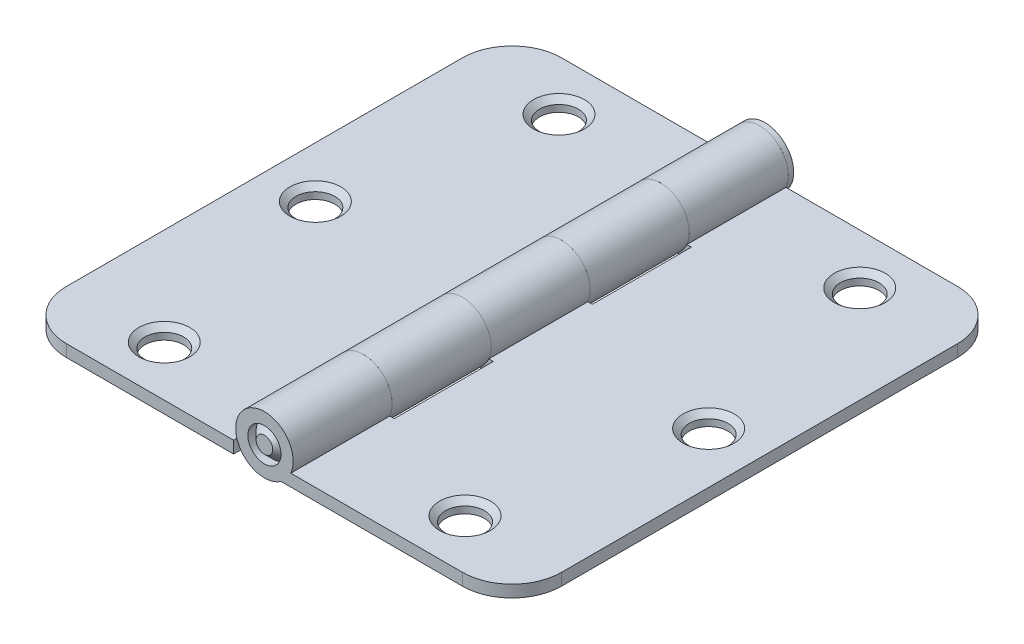
SolidWorks part; units mm, degrees
ref_plane "Front Plane" through (0, 0, 0) normal (0, 0, 1) x (1, 0, 0)
ref_plane "Top Plane" through (0, 0, 0) normal (0, 1, 0) x (1, 0, 0)
ref_plane "Right Plane" through (0, 0, 0) normal (1, 0, 0) x (0, 0, -1)
sketch "Sketch24" plane through (0, 0, 0) normal (0, 0, 1) x (1, 0, 0)
  line L0 (4.7324, -2.0552) -> (44.45, -2.0552) construction
  line L1 (44.45, -2.0552) -> (44.45, -4.2142) construction
  line L2 (44.45, -4.2142) -> (2.9766, -4.2142) construction
  line L3 (2.9766, -4.2142) -> (-2.9766, -4.2142) construction
  line L4 (-2.9766, -4.2142) -> (-44.45, -4.2142) construction
  line L5 (-44.45, -4.2142) -> (-44.45, -2.0552) construction
  line L6 (-44.45, -2.0552) -> (-4.7324, -2.0552) construction
  line L7 (-4.7324, -2.0552) -> (4.7324, -2.0552) construction
  line L8 (-5.5404, -2.0552) -> (-5.5404, -4.2142) construction
  line L9 (-5.1594, 0) -> (0, 0) construction
  line L10 (0, 0) -> (5.1594, 0) construction
  line L11 (2.9766, 0) -> (2.9766, -4.2142) construction
  circle A0 centre (0, 0) radius 2.9766 construction
  circle A1 centre (0, 0) radius 5.1594 construction
  dimension "Pin Diameter" = 5.9531
  dimension "Knuckle Diameter" = 10.3187
  dimension "Overall Width" = 88.9
  dimension "Leaf Thickness" = 2.159
  dimension "D1" = 0.381
  dimension "Door Leaf Width" = 44.45
  dimension "Frame Leaf Width" = 44.45
sketch "Sketch25" plane through (0, 0, 0) normal (0, 1, 0) x (1, 0, 0)
  line L0 (0, 0) -> (0, -44.45) construction
  line L1 (0, 0) -> (0, 44.45) construction
  line L2 (-27.0002, 0) -> (-27.0002, 35.433) construction
  line L3 (-2.9766, 0) -> (-44.45, 0) construction
  line L4 (-27.0002, 0) -> (-27.0002, -35.433) construction
  line L5 (-44.45, 0) -> (-44.45, -44.45) construction
  line L6 (-44.45, 0) -> (0, 0) construction
  line L7 (0, 0) -> (44.45, 0) construction
  line L8 (44.45, 0) -> (44.45, -44.45) construction
  circle A0 centre (-27.0002, 35.433) radius 3.4925 construction
  circle A1 centre (-27.0002, -35.433) radius 3.4925 construction
  circle A2 centre (-35.306, 0) radius 3.4925 construction
  point P10 (-30.4927, -35.433)
  point P12 (-30.4927, 35.433)
  point P13 (-27.0002, 0)
  point P14 (-27.0002, 38.9255)
  dimension "Hole Diameter" = 6.985
  dimension "Door Leaf Height" = 88.9
  dimension "Side to Side" = 27.0002
  dimension "Top to Bottom" = 70.866
  dimension "Center Side to Side" = 35.306
  dimension "Frame Leaf Height" = 88.9
sketch "Sketch1" plane through (0, 0, 0) normal (0, 0, 1) x (1, 0, 0)
  line L0 (44.45, -4.2142) -> (2.9766, -4.2142)
  line L1 (44.45, -4.2142) -> (44.45, -2.0552)
  line L2 (44.45, -2.0552) -> (4.7324, -2.0552)
  line L3 (2.9766, -4.2142) -> (2.9766, 0) construction
  line L4 (-5.1594, 0) -> (-5.1594, -4.2142) construction
  line L5 (-44.45, -2.0552) -> (-5.5404, -2.0552)
  line L6 (-44.45, -2.0552) -> (-44.45, -4.2142)
  line L7 (-44.45, -4.2142) -> (-5.5404, -4.2142)
  line L8 (-5.5404, -2.0552) -> (-5.5404, -4.2142)
  circle A0 centre (0, 0) radius 2.9766
  arc A1 (2.9766, -4.2142) -> (4.7324, -2.0552) centre (0, 0) cw
  point P5 (-2.9766, 0)
  dimension "knuckle dia" = 10.3187
  dimension "D3" = 0.381
  dimension "D4" = 44.45
  dimension "Wd" = 88.9
extrude "Extrude1" add sketch "Sketch1" against normal up to vertex (44.45 mm away) and the other way up to vertex (44.45 mm away) up to point (0, 0, -44.45) other way up to point (0, 0, 44.45)
sketch "Sketch2" plane through (0, -2.0552, 0) normal (0, 1, 0) x (1, 0, 0)
  line L1 (5.5404, 26.67) -> (-5.5404, 26.67)
  line L2 (5.5404, 26.67) -> (5.5404, 44.45)
  line L3 (5.5404, 44.45) -> (-5.5404, 44.45)
  line L4 (-5.5404, 26.67) -> (-5.5404, 44.45)
  line L5 (5.5404, -8.89) -> (-5.5404, -8.89)
  line L6 (5.5404, -8.89) -> (5.5404, 8.89)
  line L7 (5.5404, 8.89) -> (-5.5404, 8.89)
  line L8 (-5.5404, -8.89) -> (-5.5404, 8.89)
  line L9 (5.5404, -44.45) -> (-5.5404, -44.45)
  line L10 (5.5404, -44.45) -> (5.5404, -26.67)
  line L11 (5.5404, -26.67) -> (-5.5404, -26.67)
  line L12 (-5.5404, -44.45) -> (-5.5404, -26.67)
  line L14 (-5.1594, -44.45) -> (5.1594, -44.45) construction
  line L17 (5.1594, 44.45) -> (-5.1594, 44.45) construction
  line L18 (5.5404, 0) -> (-5.5404, 0) construction
  line L19 (44.45, -44.45) -> (4.7324, -44.45) construction
  line L20 (-5.1594, 44.45) -> (-5.1594, -44.45) construction
  line L21 (-5.5404, -44.45) -> (-44.45, -44.45) construction
  line L22 (5.1594, -44.45) -> (5.1594, 44.45) construction
  dimension "D3" = 0.381
  dimension "D2" = 0.381
  dimension "D1" = 17.78
sketch "Sketch6" plane through (0, 0, 0) normal (0, 1, 0) x (1, 0, 0)
  line L0 (-5.1594, 44.45) -> (-5.1594, 45.4215)
  line L1 (-5.1594, -44.45) -> (-2.9766, -44.45)
  line L2 (-2.9766, 44.45) -> (-5.1594, 44.45)
  line L3 (0, 0) -> (0, -44.45) construction
  line L4 (-5.5404, -44.45) -> (-44.45, -44.45) construction
  line L5 (-5.5404, 44.45) -> (-44.45, 44.45) construction
  line L6 (-5.1594, -45.4215) -> (-5.1594, -44.45)
  line L7 (0, 0) -> (0.9716, 0) construction
  line L8 (5.5404, -44.45) -> (-5.5404, -44.45) construction
  line L9 (44.45, 0) -> (2.9766, 0) construction
  line L10 (-2.9766, 44.45) -> (-2.9766, -44.45)
  line L11 (0, -46.3931) -> (0, 46.3931)
  arc A0 (-5.1594, -45.4215) -> (0, -46.3931) centre (0, -32.208) ccw
  arc A1 (-5.1594, 45.4215) -> (0, 46.3931) centre (0, 32.208) cw
  circle A2 centre (0, -45.4215) radius 0.9716 construction
  dimension "D1" = 1.9431
revolve "Revolve1" add sketch "Sketch6" angle 360 about L11
sketch "Sketch20" plane through (0, -2.0552, 0) normal (0, 1, 0) x (1, 0, 0)
  circle A1 centre (-27.0002, 35.433) radius 3.4925 construction
  circle A2 centre (-27.0002, 35.433) radius 3.4925
  circle A3 centre (-27.0002, -35.433) radius 3.4925 construction
  circle A4 centre (-27.0002, -35.433) radius 3.4925
  circle A5 centre (-35.306, 0) radius 3.4925 construction
  circle A6 centre (-35.306, 0) radius 3.4925
extrude "Extrude24" cut sketch "Sketch20" against normal through all
chamfer "Chamfer2" distance 1.0795 angle 41 3 edges at (-27.0002, -2.0552, 38.9255) (-27.0002, -2.0552, -31.9405) (-35.306, -2.0552, 3.4925) first distance on face at (-35.306, -2.0552, 3.4925)
mirror "Mirror2" about plane through (0, 0, 0) normal (1, 0, 0) of "Extrude24", "Chamfer2"
sketch "Sketch3" plane through (0, 0, 0) normal (0, 1, 0) x (1, 0, 0)
  line L0 (0, 8.89) -> (0, -8.89) construction
  line L1 (-5.5404, 26.67) -> (5.5404, 26.67)
  line L2 (-5.5404, 26.67) -> (-5.5404, 8.89)
  line L3 (-5.5404, 8.89) -> (5.5404, 8.89)
  line L4 (5.5404, 26.67) -> (5.5404, 8.89)
  line L5 (-5.5404, -8.89) -> (5.5404, -8.89)
  line L6 (-5.5404, -8.89) -> (-5.5404, -26.67)
  line L7 (-5.5404, -26.67) -> (5.5404, -26.67)
  line L8 (5.5404, -8.89) -> (5.5404, -26.67)
  line L9 (0, 26.67) -> (0, 44.45) construction
  line L11 (0, -26.67) -> (0, -44.45) construction
  line L13 (-5.5404, 44.45) -> (-5.5404, -44.45) construction
extrude "Cut-Extrude1" cut sketch "Sketch3" against normal mid plane 76.2
sketch "Sketch4" plane through (0, 0, -26.67) normal (0, 0, 1) x (1, 0, 0)
  line L1 (-44.45, -4.2142) -> (-5.5404, -4.2142) construction
  line L2 (-5.5404, -2.0552) -> (-4.7324, -2.0552)
  line L3 (-5.5404, -2.0552) -> (-5.5404, -4.2142)
  line L4 (-5.5404, -4.2142) -> (-2.9766, -4.2142)
  circle A0 centre (0, 0) radius 2.9766 construction
  circle A1 centre (0, 0) radius 2.9766
  arc A2 (4.7324, -2.0552) -> (2.9766, -4.2142) centre (0, 0) ccw construction
  arc A3 (-2.9766, -4.2142) -> (-4.7324, -2.0552) centre (0, 0) ccw
extrude "Extrude2" add sketch "Sketch4" along normal up to vertex (17.78 mm away) up to point (5.5404, -2.0552, -8.89)
sketch "Sketch5" plane through (0, 0, 8.89) normal (0, 0, 1) x (1, 0, 0)
  line L3 (-4.7324, -2.0552) -> (-5.5404, -2.0552)
  line L4 (-5.5404, -4.2142) -> (-2.9766, -4.2142)
  line L5 (-5.5404, -2.0552) -> (-5.5404, -4.2142)
  line L6 (-4.7324, -2.0552) -> (-5.5404, -2.0552)
  line L7 (-5.5404, -4.2142) -> (-2.9766, -4.2142)
  line L8 (-5.5404, -2.0552) -> (-5.5404, -4.2142)
  circle A1 centre (0, 0) radius 2.9766
  circle A2 centre (0, 0) radius 2.9766
  arc A3 (-2.9766, -4.2142) -> (-4.7324, -2.0552) centre (0, 0) ccw
  arc A4 (-2.9766, -4.2142) -> (-4.7324, -2.0552) centre (0, 0) ccw
  dimension "D1" = 0
  dimension "D2" = 0
extrude "Extrude3" add sketch "Sketch5" along normal up to vertex (17.78 mm away) up to point (-5.5404, -2.0552, 26.67)
sketch "Sketch19" plane through (0, 0, 0) normal (0, 1, 0) x (1, 0, 0)
  line L1 (-44.45, -44.45) -> (44.45, -44.45)
  line L2 (-44.45, -44.45) -> (-44.45, -46.3931)
  line L3 (-44.45, -46.3931) -> (44.45, -46.3931)
  line L4 (44.45, -44.45) -> (44.45, -46.3931)
  arc A0 (-5.1594, -45.4216) -> (5.1594, -45.4215) centre (0, -32.208) ccw construction
extrude "Extrude23" cut sketch "Sketch19" against normal through all and the other way through all
chamfer "Chamfer1" distance 1.4883 angle 45 1 edges at (-2.9766, 0, 44.45)
sketch "Sketch26" plane through (0, 0, 0) normal (0, 1, 0) x (1, 0, 0)
  line L0 (-44.45, 44.45) -> (-44.45, -44.45) construction
  line L1 (-5.5404, 44.45) -> (-44.45, 44.45) construction
  line L2 (-35.56, 44.45) -> (-44.45, 44.45)
  line L3 (-44.45, 44.45) -> (-44.45, 35.56)
  line L4 (44.45, 44.45) -> (4.7324, 44.45) construction
  line L5 (44.45, 44.45) -> (44.45, -44.45) construction
  line L6 (35.56, 44.45) -> (44.45, 44.45)
  line L7 (44.45, 44.45) -> (44.45, 35.56)
  line L8 (44.45, -44.45) -> (4.7324, -44.45) construction
  line L9 (-5.5404, -44.45) -> (-44.45, -44.45) construction
  line L10 (-35.56, -44.45) -> (-44.45, -44.45)
  line L11 (-44.45, -44.45) -> (-44.45, -35.56)
  line L12 (35.56, -44.45) -> (44.45, -44.45)
  line L13 (44.45, -44.45) -> (44.45, -35.56)
  arc A0 (-44.45, 35.56) -> (-35.56, 44.45) centre (-35.56, 35.56) cw
  arc A1 (35.56, 44.45) -> (44.45, 35.56) centre (35.56, 35.56) cw
  arc A2 (35.56, -44.45) -> (44.45, -35.56) centre (35.56, -35.56) ccw
  arc A3 (-44.45, -35.56) -> (-35.56, -44.45) centre (-35.56, -35.56) ccw
  dimension "D1" = 8.89
extrude "Cut-Extrude2" cut sketch "Sketch26" against normal through all both and the other way through all
equation "\"D4@Sketch1\" = \"Overall Width@Sketch24\" / 2"
equation "\"D1@Chamfer1\"= \"Pin Diameter@Sketch24\" * .25"
equation "\"D1@Chamfer2\" = \"Leaf Thickness@Sketch24\" * .5"
equation "\"D1\"= \"D1@Chamfer2\""
equation "\"D2\"= \"D2@Chamfer2\""
equation "\"D1\"= \"Overall Width@Sketch24\" * .1"
equation "\"Door Leaf Width@Sketch24\" = \"Overall Width@Sketch24\" * .5"
equation "\"Wd@Sketch1\"=\"Overall Width@Sketch24\""
equation "\"D3@Sketch1\"=\"D1@Sketch24\""
equation "\"Pin Dia@Sketch1\"=\"Pin Diameter@Sketch24\""
equation "\"Leaf thick@Sketch1\"=\"Leaf Thickness@Sketch24\""
equation "\"D1@Sketch6\"=\"Leaf thick@Sketch1\"*.9"
equation "\"D1@Sketch2\" = \"Door Leaf Height@Sketch25\" / 5"
equation "\"D1@Sketch26\"=\"Overall Width@Sketch24\" * .1"
